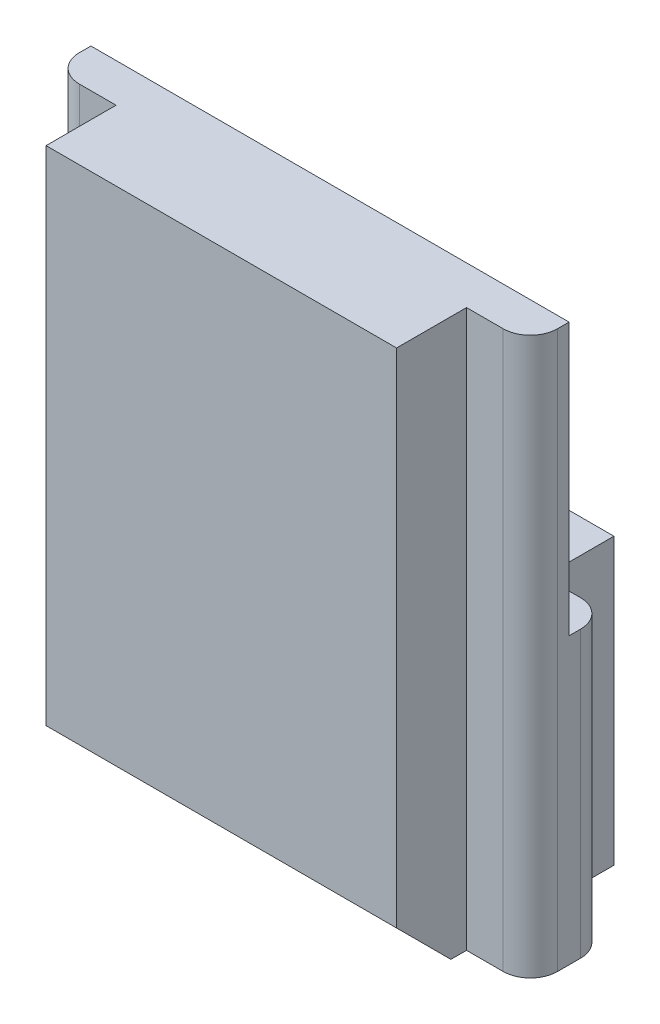
SolidWorks part; units mm, degrees
ref_plane "Plan de face" through (0, 0, 0) normal (0, 0, 1) x (1, 0, 0)
ref_plane "Plan de dessus" through (0, 0, 0) normal (0, 1, 0) x (1, 0, 0)
ref_plane "Plan de droite" through (0, 0, 0) normal (1, 0, 0) x (0, 0, -1)
sketch "Esquisse1" plane through (0, 0, 0) normal (0, 1, 0) x (1, 0, 0)
  line L0 (0, 4) -> (15.25, 4) construction
  line L1 (0, 0) -> (12.9, 0)
  line L2 (0, 0) -> (0, 8)
  line L3 (0, 8) -> (12.9, 8)
  line L4 (12.9, 0) -> (12.9, 8)
  line L6 (0, 2.575) -> (-2.35, 2.575)
  line L7 (0, 2.575) -> (0, 5.425)
  line L8 (0, 5.425) -> (-2.35, 5.425)
  line L9 (-2.35, 2.575) -> (-2.35, 5.425)
  line L10 (12.9, 2.575) -> (15.25, 2.575)
  line L11 (12.9, 2.575) -> (12.9, 5.425)
  line L12 (12.9, 5.425) -> (15.25, 5.425)
  line L13 (15.25, 2.575) -> (15.25, 5.425)
  dimension "D1" = 2.85
  dimension "D2" = 2.35
  dimension "D3" = 12.9
  dimension "D4" = 8
extrude "Boss.-Extru.1" add sketch "Esquisse1" along normal blind 20.49 contours L1 L4 L3 L2 | L6 L9 L8 L7 | L10 L13 L12 L11
chamfer "Chanfrein1" distance 2 angle 45 1 edges at (6.45, 0, 0)
sketch "Esquisse2" plane through (0, 20.49, 0) normal (0, 1, 0) x (1, 0, 0)
  line L0 (0, 0) -> (12.9, 0) construction
  line L1 (-2.35, 4) -> (15.25, 4)
  line L2 (-2.35, 4) -> (-2.35, 8)
  line L3 (-2.35, 8) -> (15.25, 8)
  line L4 (15.25, 4) -> (15.25, 8)
  line L5 (-2.35, 2.575) -> (-2.35, 5.425) construction
  line L6 (15.25, 2.575) -> (15.25, 5.425) construction
  line L7 (0, 8) -> (12.9, 8) construction
  dimension "D1" = 4
extrude "Enlèv. mat.-Extru.1" cut sketch "Esquisse2" against normal blind 10
fillet "Congé1" radius 1 4 edges at (15.25, 5.245, -5.425) (-2.35, 5.245, -5.425) (-2.35, 10.245, -2.575) (15.25, 10.245, -2.575)
